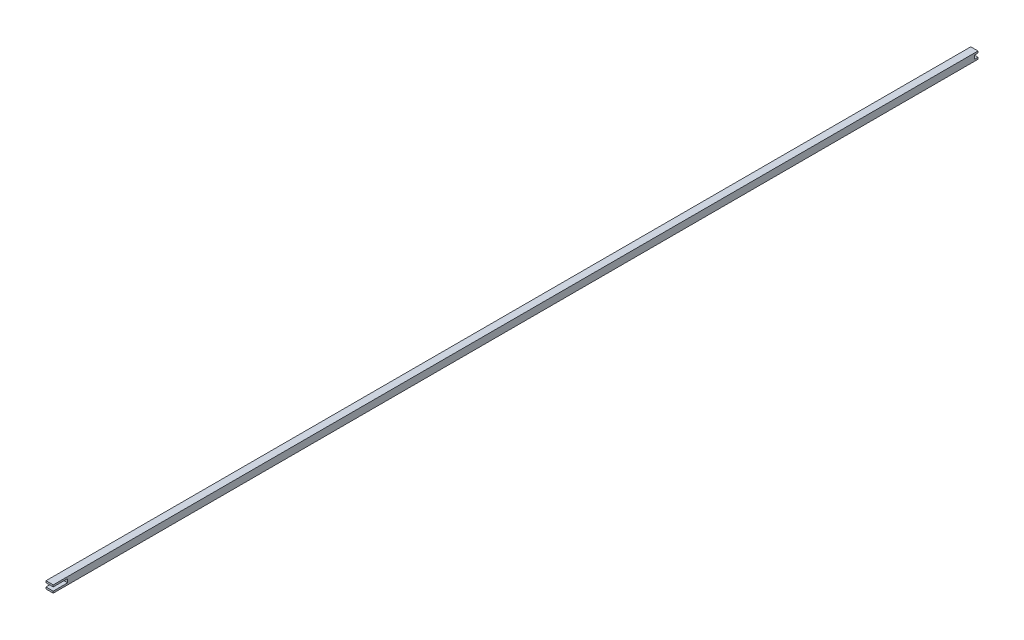
SolidWorks part; units mm, degrees
ref_plane "Front Plane" through (0, 0, 0) normal (1, 0, 0) x (0, 1, 0)
ref_plane "Top Plane" through (0, 0, 0) normal (0, 0, 1) x (0, 1, 0)
ref_plane "Right Plane" through (0, 0, 0) normal (0, 1, 0) x (-1, 0, 0)
sketch "Sketch1" plane through (0, 0, 0) normal (1, 0, 0) x (0, 1, 0)
  line L1 (3.175, 406.4) -> (-3.175, 406.4) construction
  line L2 (3.175, 406.4) -> (3.175, -406.4)
  line L3 (3.175, -406.4) -> (-3.175, -406.4) construction
  line L4 (-3.175, 406.4) -> (-3.175, -406.4)
  line L5 (3.175, 406.4) -> (-3.175, -406.4) construction
  line L6 (3.175, -406.4) -> (-3.175, 406.4) construction
  line L23 (-3.175, -406.4) -> (-1.5875, -406.4)
  line L24 (-1.5875, -403.225) -> (1.5875, -403.225)
  line L29 (-1.5875, -403.225) -> (-1.5875, -406.4)
  line L30 (-1.5875, -406.4) -> (1.5875, -406.4) construction
  line L31 (1.5875, -403.225) -> (1.5875, -406.4)
  line L32 (-1.5875, -403.225) -> (1.5875, -406.4) construction
  line L33 (-1.5875, -406.4) -> (1.5875, -403.225) construction
  line L34 (1.5875, -406.4) -> (3.175, -406.4)
  line L35 (-3.175, 406.4) -> (-1.5875, 406.4)
  line L36 (-1.5875, 406.4) -> (1.5875, 406.4) construction
  line L37 (-1.5875, 406.4) -> (-1.5875, 393.7)
  line L38 (-1.5875, 393.7) -> (1.5875, 393.7)
  line L39 (1.5875, 406.4) -> (1.5875, 393.7)
  line L40 (-1.5875, 406.4) -> (1.5875, 393.7) construction
  line L41 (-1.5875, 393.7) -> (1.5875, 406.4) construction
  line L42 (1.5875, 406.4) -> (3.175, 406.4)
  point P0 (0, 0)
  point P3 (0, -404.8125)
  point P10 (0, 400.05)
  point P11 (0, -406.4)
  point P13 (0, -406.4)
  point P18 (0, 406.4)
  point P19 (0, 406.4)
  dimension "D1" = 812.8
  dimension "D2" = 6.35
  dimension "D3" = 3.175
  dimension "D4" = 3.175
  dimension "D5" = 12.7
  dimension "D6" = 3.175
extrude "Boss-Extrude1" add sketch "Sketch1" along normal mid plane 6.35
